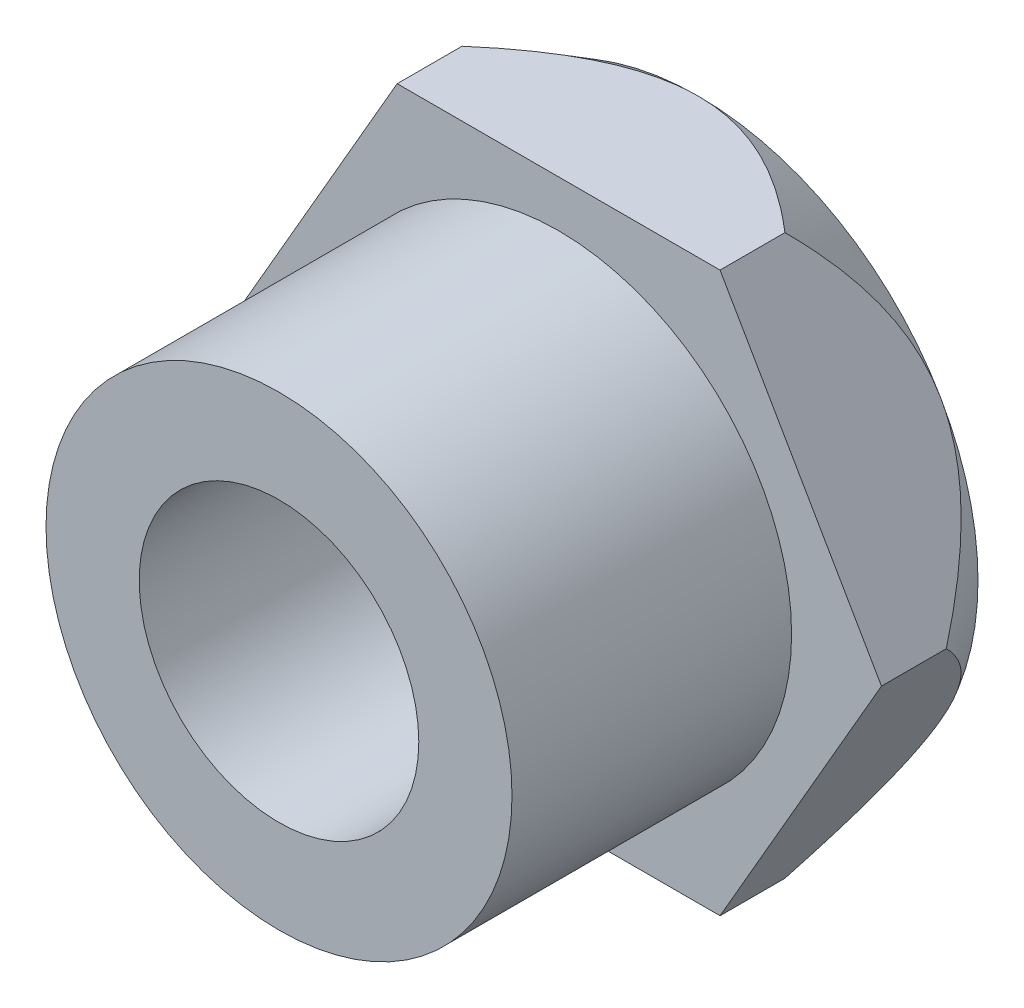
SolidWorks part; units mm, degrees
ref_plane "Front Plane" through (0, 0, 0) normal (0, 0, 1) x (1, 0, 0)
ref_plane "Top Plane" through (0, 0, 0) normal (0, 1, 0) x (1, 0, 0)
ref_plane "Right Plane" through (0, 0, 0) normal (1, 0, 0) x (0, 0, -1)
sketch "Sketch1" plane through (0, 0, 0) normal (0, 0, 1) x (1, 0, 0)
  line L1 (6.9282, 0) -> (3.4641, 6)
  line L2 (3.4641, 6) -> (-3.4641, 6)
  line L3 (-3.4641, 6) -> (-6.9282, 0)
  line L4 (-6.9282, 0) -> (-3.4641, -6)
  line L5 (-3.4641, -6) -> (3.4641, -6)
  line L6 (3.4641, -6) -> (6.9282, 0)
  circle A0 centre (0, 0) radius 5
  circle A1 centre (0, 0) radius 6 construction
  dimension "D2" = 10
  dimension "D1" = 12
extrude "Boss-Extrude1" add sketch "Sketch1" along normal blind 6 contours A0 region at (0, 0, 0)
cosmetic thread "Cosmetic Thread1" parameters "D2"=6.65
extrude "Boss-Extrude2" add sketch "Sketch1<3>" against normal blind 3 separate body contours L5 L6 L1 L2 L3 L4 A0 | A0 region at (5.0374, -2.9083, 0) region at (0, 0, 0)
sketch "Sketch1<3>" plane through (0, 0, 0) normal (0, 0, 1) x (1, 0, 0) same geometry as "Sketch1"
sketch "Sketch2" plane through (0, 0, -3) normal (0, 0, -1) x (-1, 0, 0)
  circle A0 centre (0, 0) radius 3
  dimension "D1" = 6
extrude "Cut-Extrude1" cut sketch "Sketch2" against normal blind 21
sketch "Sketch4" plane through (0, 0, -3) normal (0, 0, -1) x (-1, 0, 0)
  circle A0 centre (0, 0) radius 6
  dimension "D1" = 12
extrude "Cut-Extrude3" cut sketch "Sketch4" against normal blind 40.5 draft 30 flip side to cut
